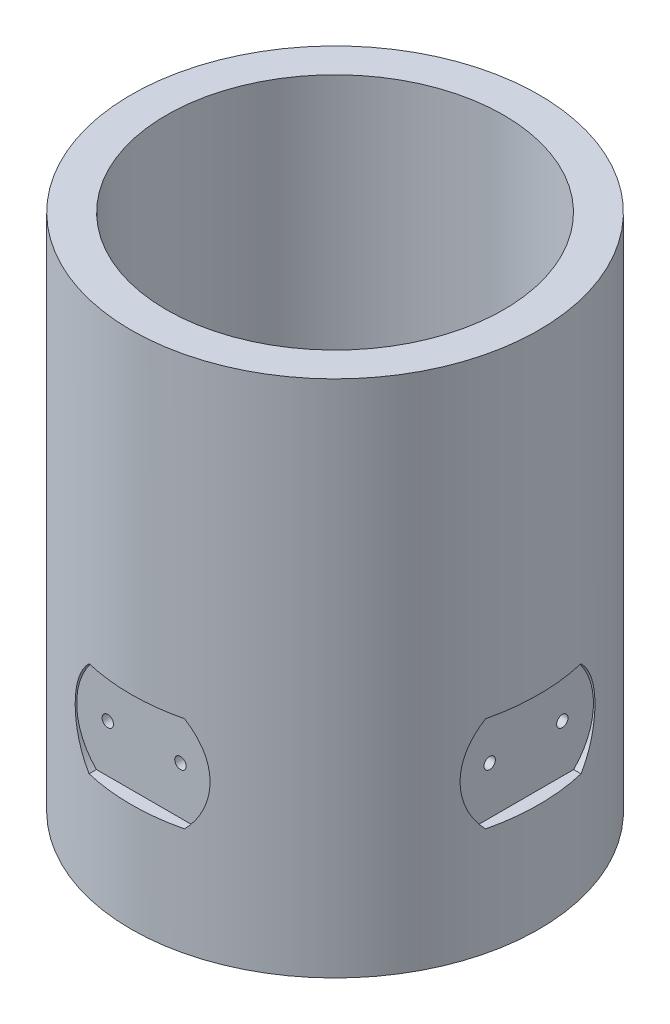
SolidWorks part; units mm, degrees
ref_plane "Front Plane" through (0, 0, 0) normal (0, 0, 1) x (1, 0, 0)
ref_plane "Top Plane" through (0, 0, 0) normal (0, 1, 0) x (1, 0, 0)
ref_plane "Right Plane" through (0, 0, 0) normal (1, 0, 0) x (0, 0, -1)
sketch "Sketch2" plane through (0, 0, 0) normal (0, 1, 0) x (1, 0, 0)
  circle A0 centre (0, 0) radius 39.3
  circle A1 centre (0, 0) radius 32.5
  dimension "D1" = 78.6
  dimension "D2" = 65
extrude "Boss-Extrude1" add sketch "Sketch2" along normal blind 100
sketch "Sketch3" plane through (0, 0, 0) normal (0, 0, 1) x (1, 0, 0)
  line L1 (9.1924, 39.1924) -> (-9.1924, 39.1924)
  line L3 (-9.1924, 20.8076) -> (9.1924, 20.8076)
  arc A0 (-9.1924, 39.1924) -> (-9.1924, 20.8076) centre (0, 30) ccw
  arc A1 (9.1924, 20.8076) -> (9.1924, 39.1924) centre (0, 30) ccw
  dimension "D1" = 26
  dimension "D2" = 30
extrude "Cut-Extrude1" cut sketch "Sketch3" against normal blind 2.5 from offset 39.3
ref_axis "Axis1" through (0, 100, 0) along (0, -1, 0)
sketch "Sketch4" plane through (0, 0, 36.8) normal (0, 0, 1) x (1, 0, 0)
  circle A2 centre (7, 30) radius 1.1
  circle A3 centre (-7, 30) radius 1.1
  dimension "D1" = 2.2
  dimension "D2" = 2.2
extrude "Cut-Extrude2" cut sketch "Sketch4" against normal blind 3
pattern_circular "CirPattern1" count 4 over 360 about axis through (0, 100, 0) along (0, -1, 0) of "Cut-Extrude1", "Cut-Extrude2"
